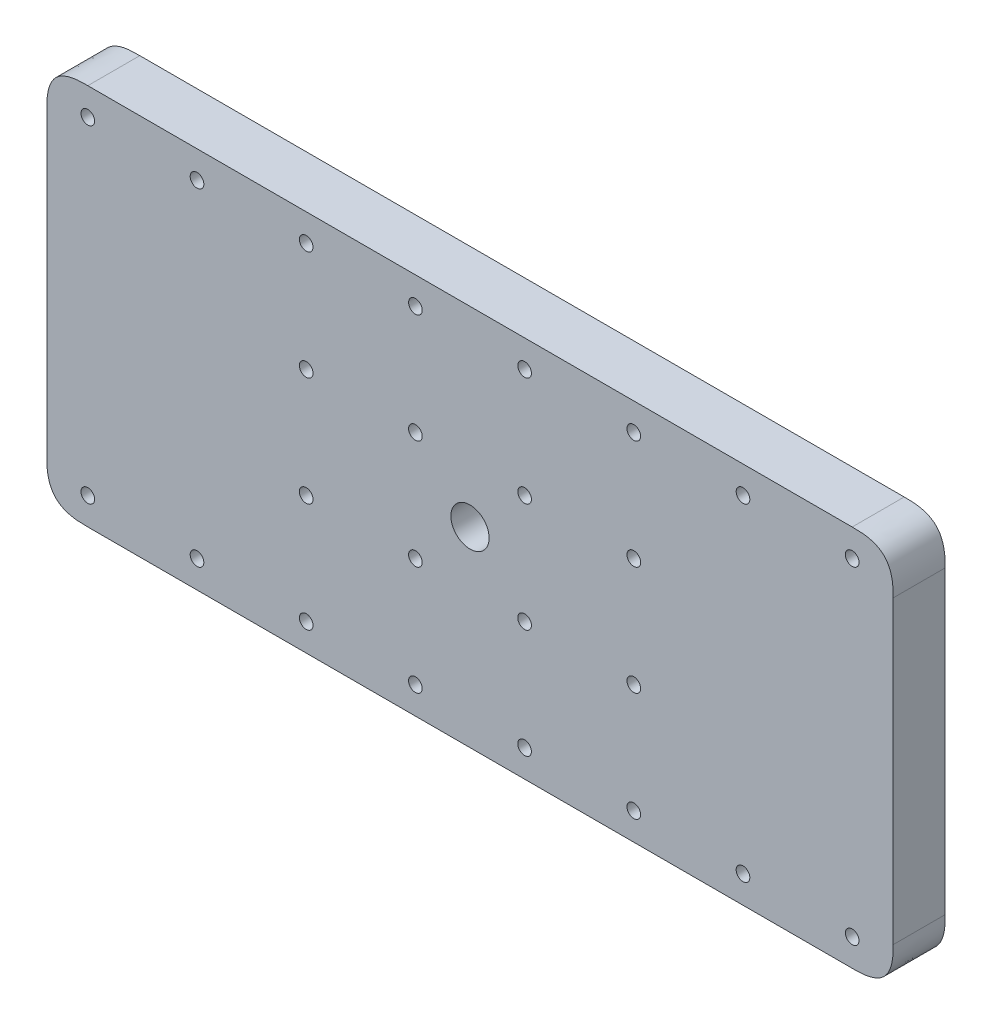
SolidWorks part; units mm, degrees
ref_plane "Front Plane" through (0, 0, 0) normal (0, 0, 1) x (1, 0, 0)
ref_plane "Top Plane" through (0, 0, 0) normal (0, 1, 0) x (1, 0, 0)
ref_plane "Right Plane" through (0, 0, 0) normal (1, 0, 0) x (0, 0, -1)
sketch "Sketch1" plane through (0, 0, 0) normal (0, 0, 1) x (1, 0, 0)
  line L1 (-155, 70) -> (155, 70)
  line L2 (-155, 70) -> (-155, -70)
  line L3 (-155, -70) -> (155, -70)
  line L4 (155, 70) -> (155, -70)
  line L5 (-155, 70) -> (155, -70) construction
  line L6 (-155, -70) -> (155, 70) construction
  point P0 (0, 0)
  dimension "D1" = 310
  dimension "D2" = 140
extrude "Boss-Extrude1" add sketch "Sketch1" along normal blind 19.05
sketch "Sketch5" plane through (0, 0, 19.05) normal (0, 0, 1) x (1, 0, 0)
  line L1 (-140, 60) -> (140, 60) construction
  line L2 (-140, 60) -> (-140, -60) construction
  line L3 (-140, -60) -> (140, -60) construction
  line L4 (140, 60) -> (140, -60) construction
  line L8 (-140, 60) -> (140, -60) construction
  point P0 (-140, 60)
  point P14 (-140, 60)
  dimension "D1" = 280
  dimension "D2" = 120
hole_wizard "Tap Drill for M6x1.0 Tap1" positions "Sketch5" profile "Sketch6" hole size "M6x1.0" standard "ANSI Metric" end condition up to next
sketch "Sketch6" plane through (-140, 60, 19.05) normal (1, 0, 0) x (0, -1, 0)
  line L0 (0, 0) -> (0, 19.05)
  line L1 (0, 19.05) -> (2.5, 19.05)
  line L2 (2.5, 19.05) -> (2.5, 0)
  line L5 (2.5, 0) -> (0, 0)
  line L11 (0, -6.35) -> (0, 107.95) construction
  dimension "Thru Hole Dia." = 5
  dimension "Thru Hole Depth" = 19.05
pattern_linear "LPattern1" count 8 spacing 40 along (1, 0, 0) count 4 spacing 40 along (0, -1, 0) skipping (0, 1), (0, 2), (1, 1), (1, 2), (6, 1), (6, 2), (7, 1), (7, 2) of "Tap Drill for M6x1.0 Tap1"
fillet "Fillet1" radius 15 4 edges at (155, -70, 9.525) (155, 70, 9.525) (-155, 70, 9.525) (-155, -70, 9.525) curvature continuous yes
sketch "Sketch10" plane through (0, 0, 0) normal (0, 0, -1) x (-1, 0, 0)
  point P0 (137.5, -12.5)
  point P3 (137.5, 12.5)
  point P6 (112.5, 12.5)
  point P9 (112.5, -12.5)
  point P12 (-112.5, -12.5)
  point P15 (-137.5, -12.5)
  point P18 (-112.5, 12.5)
  point P21 (-137.5, 12.5)
hole_wizard "M6 Clearance Hole1" positions "Sketch10" profile "Sketch9" hole size "M6" standard "ANSI Metric"
sketch "Sketch9" plane through (-137.5, -12.5, 0) normal (1, 0, 0) x (0, 1, 0)
  line L0 (0, 0) -> (0, 14.6228)
  line L1 (0, 14.6228) -> (3.2, 12.7)
  line L2 (3.2, 12.7) -> (3.2, 0)
  line L5 (3.2, 0) -> (0, 0)
  line L10 (0, 14.6228) -> (-3.2, 12.7) construction
  line L11 (0, -6.35) -> (0, 107.95) construction
  dimension "Hole Dia." = 6.4
  dimension "Hole Depth" = 12.7
  dimension "Drill Angle" = 118
sketch "Sketch11" plane through (0, 0, 19.05) normal (0, 0, 1) x (1, 0, 0)
  line L0 (0, 70) -> (0, -70) construction
  line L1 (140, 70) -> (-140, 70) construction
  line L2 (-140, -70) -> (140, -70) construction
  point P6 (0, 0)
sketch "Sketch14" plane through (0, 0, 19.05) normal (0, 0, 1) x (1, 0, 0)
  point P0 (0, 0)
hole_wizard "Tap Drill for M16x2.0 Tap1" positions "Sketch14" profile "Sketch13" hole size "M16x2.0" standard "ANSI Metric" end condition through all
sketch "Sketch13" plane through (0, 0, 19.05) normal (1, 0, 0) x (0, -1, 0)
  line L0 (0, 0) -> (0, 19.1)
  line L1 (0, 19.1) -> (7, 19.1)
  line L2 (7, 19.1) -> (7, 0)
  line L5 (7, 0) -> (0, 0)
  line L11 (0, -6.35) -> (0, 107.95) construction
  dimension "Thru Hole Dia." = 14
  dimension "Thru Hole Depth" = 19.1
